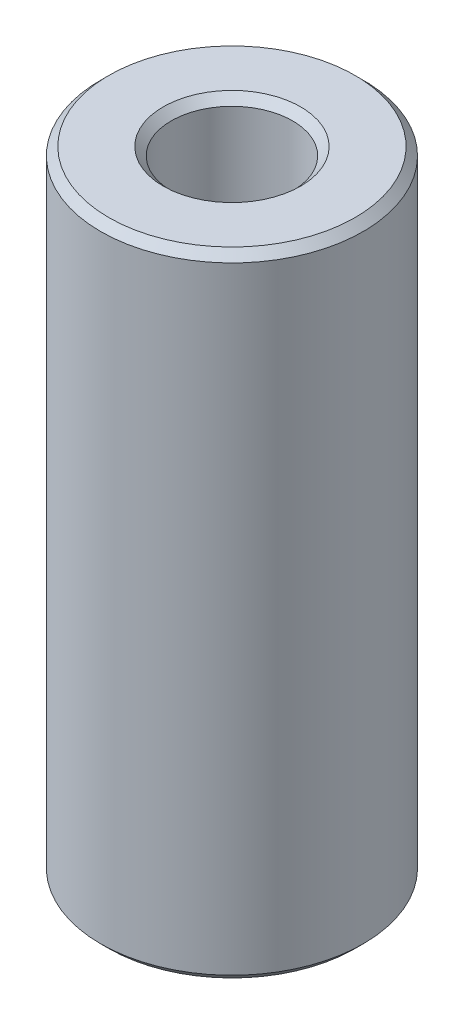
SolidWorks part; units mm, degrees
ref_plane "Front Plane" through (0, 0, 0) normal (0, 0, 1) x (1, 0, 0)
ref_plane "Top Plane" through (0, 0, 0) normal (0, 1, 0) x (1, 0, 0)
ref_plane "Right Plane" through (0, 0, 0) normal (1, 0, 0) x (0, 0, -1)
sketch "Sketch1" plane through (0, 0, 0) normal (0, 1, 0) x (1, 0, 0)
  circle A0 centre (0, 0) radius 15
  dimension "SLEEVE_OD" = 30
extrude "Boss-Extrude1" add sketch "Sketch1" along normal blind 72.3607
sketch "Sketch2" plane through (0, 0, 0) normal (0, 1, 0) x (1, 0, 0)
  circle A0 centre (0, 0) radius 6.934
  dimension "BORE_D" = 13.868
extrude "Cut-Extrude1" cut sketch "Sketch2" along normal through all
chamfer "Chamfer1" distance 0.9226 angle 45 4 edges at (0, 72.3607, 6.934) (0, 0, 6.934) (0, 0, 15) (0, 72.3607, 15)
